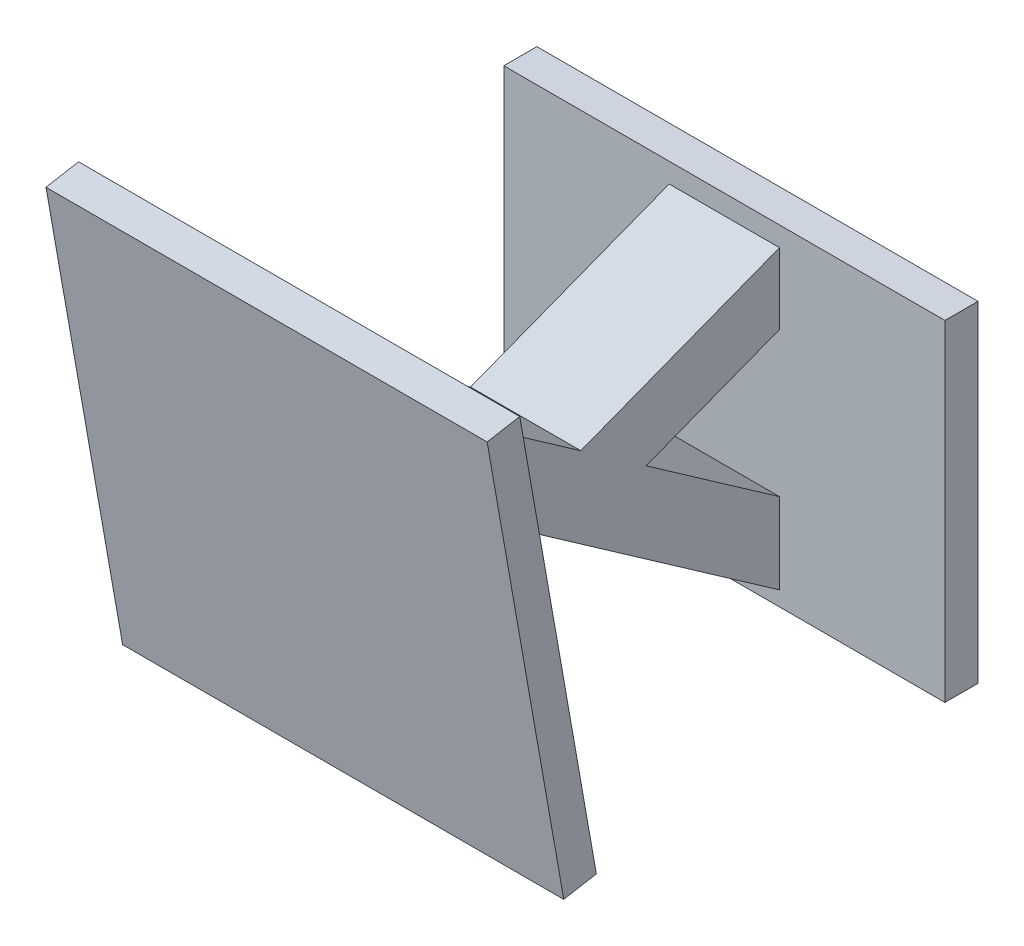
SolidWorks part; units mm, degrees
ref_plane "Front Plane" through (0, 0, 0) normal (0, 0, 1) x (1, 0, 0)
ref_plane "Top Plane" through (0, 0, 0) normal (0, 1, 0) x (1, 0, 0)
ref_plane "Right Plane" through (0, 0, 0) normal (1, 0, 0) x (0, 0, -1)
sketch "Sketch2" plane through (0, 0, 0) normal (1, 0, 0) x (0, 0, -1)
  line L0 (0, -127.6037) -> (0, -83.7743) construction
  line L1 (0, -127.6037) -> (0, -83.7743) construction
  line L2 (0, -90.689) -> (0, -120.689)
  line L3 (-3, -90.689) -> (-3, -120.689)
  line L4 (0, -90.689) -> (-3, -90.689)
  line L5 (0, -120.689) -> (-3, -120.689)
  line L6 (-3, -115.689) -> (-39.8618, -89.878) construction
  line L7 (-3, -95.689) -> (-21.4309, -102.7835) construction
  line L8 (-3, -112.0266) -> (-15.0935, -103.5586)
  line L9 (-3, -119.3513) -> (-38.8609, -94.2412)
  line L10 (-3, -92.4744) -> (-21.0183, -99.4101)
  line L11 (-3, -98.9035) -> (-15.0935, -103.5586)
  line L12 (-4.7207, -118.1464) -> (-41.5826, -92.3355) construction
  line L13 (-4.0777, -92.8892) -> (-22.5086, -99.9837) construction
  line L14 (-21.0183, -99.4101) -> (-40.3343, -85.8848)
  line L15 (-1.9223, -98.4887) -> (-20.3532, -105.5832) construction
  line L16 (-1.2793, -113.2315) -> (-38.1411, -87.4206) construction
  line L17 (-43.0335, -79.2155) -> (-36.0875, -118.6078) construction
  line L18 (-44.5107, -79.4759) -> (-37.5648, -118.8682)
  line L19 (-41.5563, -78.955) -> (-34.6103, -118.3473)
  line L20 (-44.5107, -79.4759) -> (-41.5563, -78.955)
  line L21 (-34.6103, -118.3473) -> (-37.5648, -118.8682)
  point P5 (0, -105.689)
  point P28 (-39.8618, -89.878)
  dimension "D1" = 30
  dimension "D3" = 5
  dimension "D4" = 55
  dimension "D5" = 5
  dimension "D6" = 45
  dimension "D11" = 45
  dimension "D14" = 40
  dimension "D2" = 3
  dimension "D7" = 3
  dimension "D8" = 3
  dimension "D9" = 3
  dimension "D10" = 3
  dimension "D12" = 1.5
  dimension "D13" = 1.5
extrude "Boss-Extrude1" add sketch "Sketch2" along normal mid plane 10 contours L14 L19 L9 L3 L8 L11 L10 region at (0, -101.6727, 18.4689)
sketch "Sketch3" plane through (0, 0, 0) normal (1, 0, 0) x (0, 0, -1)
  line L0 (-3, -112.0266) -> (-15.0935, -103.5586) construction
  line L1 (-3, -98.9035) -> (-15.0935, -103.5586) construction
  line L2 (-3, -92.4744) -> (-21.0183, -99.4101) construction
  line L3 (-21.0183, -99.4101) -> (-40.3343, -85.8848) construction
  line L4 (0, -120.689) -> (0, -90.689)
  line L5 (-3, -120.689) -> (0, -120.689)
  line L6 (-3, -90.689) -> (-3, -120.689)
  line L7 (0, -90.689) -> (-3, -90.689)
  line L8 (0, -120.689) -> (0, -90.689)
  line L9 (-3, -120.689) -> (0, -120.689)
  line L10 (-3, -90.689) -> (-3, -120.689)
  line L11 (0, -90.689) -> (-3, -90.689)
  line L12 (-44.5107, -79.4759) -> (-37.5648, -118.8682)
  line L13 (-37.5648, -118.8682) -> (-34.6103, -118.3473)
  line L14 (-34.6103, -118.3473) -> (-41.5563, -78.955)
  line L15 (-41.5563, -78.955) -> (-44.5107, -79.4759)
  line L16 (-44.5107, -79.4759) -> (-37.5648, -118.8682)
  line L17 (-37.5648, -118.8682) -> (-34.6103, -118.3473)
  line L18 (-34.6103, -118.3473) -> (-41.5563, -78.955)
  line L19 (-41.5563, -78.955) -> (-44.5107, -79.4759)
  line L20 (-3, -119.3513) -> (-38.8609, -94.2412) construction
  line L21 (-3, -112.0266) -> (-15.0935, -103.5586)
  line L22 (-3, -98.9035) -> (-15.0935, -103.5586)
  line L23 (-3, -92.4744) -> (-21.0183, -99.4101)
  line L24 (-21.0183, -99.4101) -> (-40.3343, -85.8848)
  line L25 (-3, -119.3513) -> (-38.8609, -94.2412)
  dimension "D1" = 0
  dimension "D2" = 0
extrude "Boss-Extrude2" add sketch "Sketch3" along normal mid plane 40 contours L8 L11 L10 L9 | L16 L17 L18 L19 region at (0, -105.689, 1.5)
